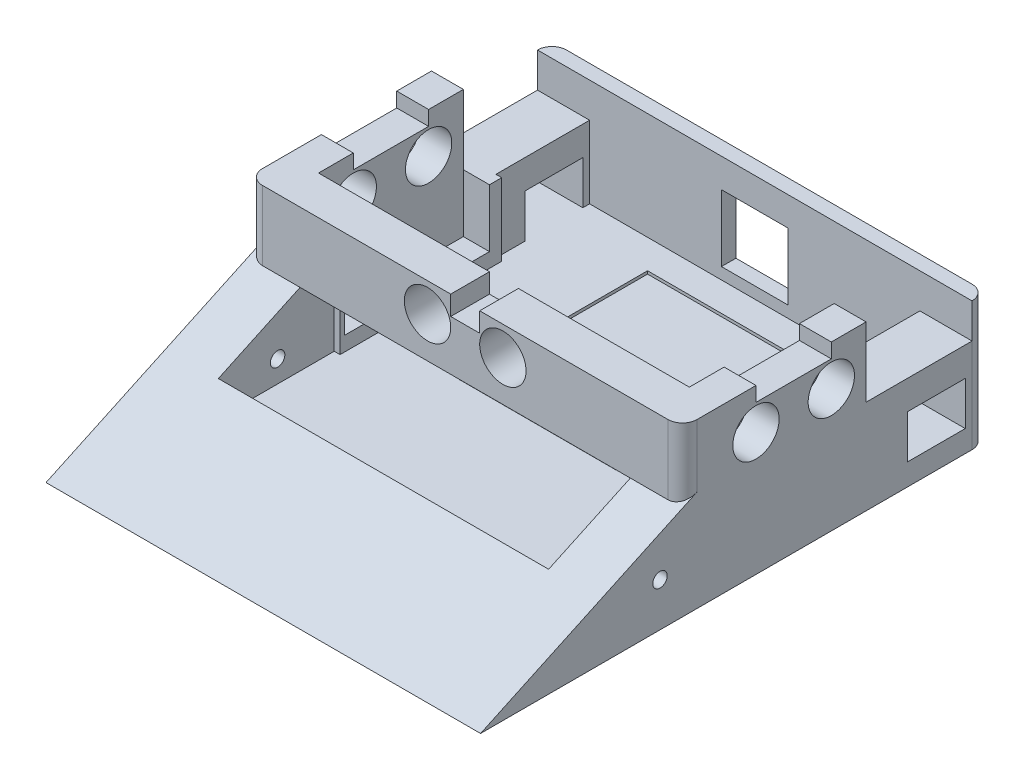
SolidWorks part; units mm, degrees
ref_plane "Front Plane" through (0, 0, 0) normal (0, 0, 1) x (1, 0, 0)
ref_plane "Top Plane" through (0, 0, 0) normal (0, 1, 0) x (1, 0, 0)
ref_plane "Right Plane" through (0, 0, 0) normal (1, 0, 0) x (0, 0, -1)
sketch "Sketch1" plane through (0, 0, 0) normal (0, 1, 0) x (1, 0, 0)
  line L4 (0, 0) -> (150, 0)
  line L5 (150, 0) -> (150, 180)
  line L6 (150, 180) -> (0, 180)
  line L7 (0, 180) -> (0, 0)
extrude "Boss-Extrude2" add sketch "Sketch1" along normal blind 7.5 contours L7 L4 L5 L6
sketch "Sketch2" plane through (150, 0, 0) normal (1, 0, 0) x (0, 0, -1)
  line L0 (180, 7.5) -> (50, 7.5)
  line L2 (50, 7.5) -> (56.85, 7.5)
  line L6 (56.85, 7.5) -> (56.85, 22.5)
  line L7 (56.85, 22.5) -> (76.85, 22.5)
  line L8 (76.85, 22.5) -> (76.85, 7.5)
  line L9 (76.85, 7.5) -> (86.85, 7.5)
  line L10 (86.85, 7.5) -> (86.85, 32.5)
  line L11 (86.85, 32.5) -> (46.85, 32.5)
  line L12 (46.85, 32.5) -> (46.85, 7.5)
  line L13 (46.85, 7.5) -> (56.85, 7.5)
  line L14 (180, 7.5) -> (172.6599, 7.5)
  line L15 (172.6599, 7.5) -> (172.6599, 22.5)
  line L16 (172.6599, 22.5) -> (152.6599, 22.5)
  line L17 (152.6599, 22.5) -> (152.6599, 7.5)
  line L18 (152.6599, 7.5) -> (142.6599, 7.5)
  line L19 (142.6599, 7.5) -> (142.6599, 32.5)
  line L20 (142.6599, 32.5) -> (180, 32.5)
  line L21 (180, 32.5) -> (180, 7.5)
  line M8 (180, 7.5) -> (0, 7.5)
extrude "Boss-Extrude4" add sketch "Sketch2" against normal blind 18 contours L11 L12 L0 L6 L7 L8 L10 M8 | L21 L20 L19 L17 L16 L15 M8 region at (150, 7.9717, -81.85) region at (150, 7.9494, -176.3299)
sketch "Sketch4" plane through (0, 0, 0) normal (-1, 0, 0) x (0, 0, 1)
  line L0 (-180, 7.5) -> (-180, 32.5)
  line L1 (-180, 32.5) -> (-142.6599, 32.5)
  line L2 (-142.6599, 32.5) -> (-142.6599, 7.5)
  line L3 (-142.6599, 7.5) -> (-152.6599, 7.5)
  line L4 (-152.6599, 7.5) -> (-152.6599, 22.5)
  line L5 (-152.6599, 22.5) -> (-172.6599, 22.5)
  line L6 (-172.6599, 22.5) -> (-172.6599, 7.5)
  line L7 (-172.6599, 7.5) -> (-180, 7.5)
  line L8 (-86.85, 7.5) -> (-86.85, 32.5)
  line L9 (-86.85, 32.5) -> (-46.85, 32.5)
  line L10 (-46.85, 32.5) -> (-46.85, 7.5)
  line L11 (-46.85, 7.5) -> (-56.85, 7.5)
  line L12 (-56.85, 7.5) -> (-56.85, 22.5)
  line L13 (-56.85, 22.5) -> (-76.85, 22.5)
  line L14 (-76.85, 22.5) -> (-76.85, 7.5)
  line L15 (-76.85, 7.5) -> (-86.85, 7.5)
extrude "Boss-Extrude5" add sketch "Sketch4" against normal blind 18
sketch "Sketch6" plane through (150, 0, 0) normal (1, 0, 0) x (0, 0, -1)
  line L1 (56.85, 7.5) -> (76.85, 7.5)
  line L2 (56.85, 7.5) -> (56.85, 22.5)
  line L3 (56.85, 22.5) -> (76.85, 22.5)
  line L4 (76.85, 7.5) -> (76.85, 22.5)
extrude "Boss-Extrude7" add sketch "Sketch6" against normal blind 18
sketch "Sketch7" plane through (150, 0, 0) normal (1, 0, 0) x (0, 0, -1)
  line L1 (162.6599, 22.5) -> (162.6599, 7.5) construction
  line L2 (172.6599, 22.5) -> (152.6599, 22.5) construction
  line L3 (152.6599, 15) -> (172.6599, 15) construction
  line L4 (152.6599, 22.5) -> (152.6599, 7.5) construction
  line L5 (172.6599, 7.5) -> (172.6599, 22.5) construction
  circle A0 centre (67.3, 15) radius 2.5
extrude "Boss-Extrude8" add sketch "Sketch7" along normal blind 22 and the other way blind 172
sketch "Sketch8" plane through (0, 0, 0) normal (-1, 0, 0) x (0, 0, 1)
  line L1 (-76.85, 7.5) -> (-56.85, 7.5)
  line L2 (-76.85, 7.5) -> (-76.85, 22.5)
  line L3 (-76.85, 22.5) -> (-56.85, 22.5)
  line L4 (-56.85, 7.5) -> (-56.85, 22.5)
extrude "Boss-Extrude9" add sketch "Sketch8" against normal blind 18
sketch "Sketch9" plane through (150, 0, 0) normal (1, 0, 0) x (0, 0, -1)
  line L0 (86.85, 32.5) -> (142.6599, 32.5)
  line L1 (142.6599, 32.5) -> (142.6599, 7.5)
  line L2 (142.6599, 7.5) -> (86.85, 7.5)
  line L3 (86.85, 7.5) -> (86.85, 32.5)
extrude "Boss-Extrude10" add sketch "Sketch9" against normal blind 20
sketch "Sketch10" plane through (0, 0, 0) normal (-1, 0, 0) x (0, 0, 1)
  line L1 (-142.6599, 7.5) -> (-86.85, 7.5)
  line L2 (-142.6599, 7.5) -> (-142.6599, 32.5)
  line L3 (-142.6599, 32.5) -> (-86.85, 32.5)
  line L4 (-86.85, 7.5) -> (-86.85, 32.5)
extrude "Boss-Extrude11" add sketch "Sketch10" against normal blind 20
chamfer "Chamfer2" distance 10 angle 65 1 edges at (75, 7.5, 0) first distance on face at (75, 3.75, 0)
sketch "Sketch12" plane through (150, 0, 0) normal (1, 0, 0) x (0, 0, -1)
  line L0 (113.425, 32.5) -> (126.425, 32.5)
  line L3 (180, 32.5) -> (46.85, 32.5) construction
  line L4 (113.425, 32.5) -> (100.425, 32.5)
  line L8 (88.425, 42.5) -> (88.425, 32.5)
  line L9 (88.425, 42.5) -> (88.425, 54.5)
  line L11 (138.425, 42.5) -> (138.425, 54.5)
  line L12 (138.425, 54.5) -> (88.425, 54.5)
  line L13 (138.425, 42.5) -> (138.425, 32.5)
  line L14 (138.425, 32.5) -> (88.425, 32.5)
  circle A1 centre (100.425, 42.5) radius 8
  circle A2 centre (126.425, 42.5) radius 8
  line M13 (180, 32.5) -> (46.85, 32.5)
extrude "Boss-Extrude12" add sketch "Sketch12" against normal blind 11 contours L13 L11 L12 L9 L8 A2 A1 M13 region at (150, 44.0762, -113.425)
sketch "Sketch13" plane through (150, 0, 0) normal (1, 0, 0) x (0, 0, -1)
  line L0 (88.425, 54.5) -> (88.425, 56.5)
  line L1 (88.425, 54.5) -> (138.425, 54.5)
  line L2 (138.425, 54.5) -> (138.425, 56.5)
  line L3 (138.425, 56.5) -> (88.425, 56.5)
extrude "Boss-Extrude13" add sketch "Sketch13" against normal blind 11
sketch "Sketch14" plane through (150, 0, 0) normal (1, 0, 0) x (0, 0, -1)
  line L0 (100.425, 51.4481) -> (100.425, 55.8735)
  line L1 (126.425, 51.4481) -> (126.425, 55.8735)
  line L2 (126.425, 55.8735) -> (100.425, 55.8735)
  line L3 (100.425, 51.4481) -> (126.425, 51.4481)
extrude "Cut-Extrude1" cut sketch "Sketch14" against normal blind 11
sketch "Sketch15" plane through (0, 32.5, 0) normal (0, 1, 0) x (1, 0, 0)
  line L0 (130, 142.6599) -> (130, 86.85) construction
  line L1 (139, 138.425) -> (130, 138.425)
  line L2 (139, 138.425) -> (139, 88.441)
  line L3 (139, 88.441) -> (130, 88.441)
  line L4 (130, 138.425) -> (130, 88.441)
extrude "Cut-Extrude2" cut sketch "Sketch15" against normal blind 20
sketch "Sketch16" plane through (0, 0, 0) normal (-1, 0, 0) x (0, 0, 1)
  line L0 (-126.425, 55.8735) -> (-126.425, 51.4481)
  line L1 (-126.425, 51.4481) -> (-100.425, 51.4481)
  line L2 (-100.425, 51.4481) -> (-100.425, 55.8735)
  line L3 (-100.425, 55.8735) -> (-126.425, 55.8735)
  line L5 (-138.425, 32.5) -> (-88.425, 32.5)
  line L6 (-138.425, 32.5) -> (-138.425, 56.5)
  line L7 (-138.425, 56.5) -> (-88.425, 56.5)
  line L8 (-88.425, 32.5) -> (-88.425, 56.5)
  circle A0 centre (-126.425, 42.5) radius 8
  circle A1 centre (-100.425, 42.5) radius 8
extrude "Boss-Extrude14" add sketch "Sketch16" against normal blind 11
sketch "Sketch17" plane through (0, 32.5, 0) normal (0, 1, 0) x (1, 0, 0)
  line L0 (20, 86.85) -> (20, 142.6599) construction
  line L1 (11, 138.425) -> (20, 138.425)
  line L2 (11, 138.425) -> (11, 88.4285)
  line L3 (11, 88.4285) -> (20, 88.4285)
  line L4 (20, 138.425) -> (20, 88.4285)
extrude "Cut-Extrude3" cut sketch "Sketch17" against normal blind 20
sketch "Sketch20" plane through (0, 7.5, 0) normal (0, 1, 0) x (1, 0, 0)
  line L0 (18, 180) -> (18, 175)
  line L1 (18, 142.6599) -> (18, 180) construction
  line L2 (18, 175) -> (132, 175)
  line L3 (132, 180) -> (132, 172.6599) construction
  line L4 (132, 175) -> (132, 180)
  line L5 (132, 180) -> (18, 180)
extrude "Boss-Extrude15" add sketch "Sketch20" along normal blind 25
sketch "Sketch21" plane through (0, 7.5, 0) normal (0, 1, 0) x (1, 0, 0)
  line L0 (75, 175) -> (75, 165)
  line L1 (18, 175) -> (132, 175) construction
  line L2 (75, 165) -> (102, 165)
  line L3 (102, 165) -> (102, 100)
  line L4 (102, 100) -> (48, 100)
  line L5 (48, 100) -> (48, 165)
  line L6 (48, 165) -> (75, 165)
extrude "Cut-Extrude4" cut sketch "Sketch21" against normal blind 1 contours L6 L5 L4 L3 L2 region at (75, 7.5, -132.5)
sketch "Sketch22" plane through (150, 0, 0) normal (1, 0, 0) x (0, 0, -1)
  line L0 (21.4451, 7.5) -> (46.85, 19.3465)
  line L1 (46.85, 32.5) -> (46.85, 7.5) construction
  line L2 (46.85, 19.3465) -> (75.0577, 32.5)
  line L3 (88.425, 32.5) -> (46.85, 32.5) construction
  line L4 (75.0577, 32.5) -> (21.4451, 32.5)
  line L5 (21.4451, 32.5) -> (21.4451, 7.5)
extrude "Cut-Extrude5" cut sketch "Sketch22" against normal blind 20
sketch "Sketch23" plane through (150, 0, 0) normal (1, 0, 0) x (0, 0, -1)
  line L0 (21.4451, 7.5) -> (46.85, 19.3465)
  line L1 (46.85, 19.3465) -> (46.85, 7.5)
  line L2 (46.85, 7.5) -> (21.4451, 7.5)
extrude "Boss-Extrude16" add sketch "Sketch23" against normal blind 50
sketch "Sketch24" plane through (0, 0, 0) normal (-1, 0, 0) x (0, 0, 1)
  line L0 (-21.4451, 7.5) -> (-75.0577, 32.5)
  line L1 (-21.4451, 7.5) -> (-21.4451, 32.5)
  line L2 (-21.4451, 32.5) -> (-75.0577, 32.5)
extrude "Cut-Extrude6" cut sketch "Sketch24" against normal blind 50
sketch "Sketch25" plane through (0, 0, 0) normal (-1, 0, 0) x (0, 0, 1)
  line L0 (-46.85, 19.3465) -> (-46.85, 7.5)
  line L1 (-46.85, 7.5) -> (-21.4451, 7.5)
  line L2 (-21.4451, 7.5) -> (-46.85, 19.3465)
extrude "Boss-Extrude17" add sketch "Sketch25" against normal blind 50
sketch "Sketch27" plane through (0, 0, -180) normal (0, 0, -1) x (-1, 0, 0)
  line L0 (-150, 32.5) -> (-150, 44.5)
  line L1 (-150, 56.5) -> (-150, 32.5) construction
  line L2 (-150, 44.5) -> (0, 44.5)
  line L3 (0, 56.5) -> (0, 32.5) construction
  line L4 (0, 44.5) -> (0, 32.5)
  line L5 (0, 32.5) -> (-150, 32.5)
extrude "Boss-Extrude18" add sketch "Sketch27" against normal blind 5
sketch "Sketch28" plane through (0, 0, -180) normal (0, 0, -1) x (-1, 0, 0)
  line L2 (-75, 34.5) -> (-63.5, 34.5)
  line L3 (-63.5, 34.5) -> (-63.5, 11.5)
  line L4 (-63.5, 11.5) -> (-86.5, 11.5)
  line L5 (-86.5, 11.5) -> (-86.5, 34.5)
  line L6 (-86.5, 34.5) -> (-75, 34.5)
extrude "Cut-Extrude7" cut sketch "Sketch28" against normal blind 5
sketch "Sketch29" plane through (0, 32.5, 0) normal (0, 1, 0) x (1, 0, 0)
  line L1 (0, 75.0577) -> (150, 75.0577)
  line L2 (0, 75.0577) -> (0, 88.425)
  line L3 (0, 88.425) -> (150, 88.425)
  line L4 (150, 75.0577) -> (150, 88.425)
extrude "Boss-Extrude19" add sketch "Sketch29" along normal blind 24
sketch "Sketch30" plane through (0, 7.5, 0) normal (0, 1, 0) x (1, 0, 0)
  line L1 (50, 21.4451) -> (100, 21.4451)
  line L2 (50, 21.4451) -> (50, 46.85)
  line L3 (50, 46.85) -> (100, 46.85)
  line L4 (100, 21.4451) -> (100, 46.85)
extrude "Boss-Extrude20" add sketch "Sketch30" along normal blind 12
sketch "Sketch31" plane through (100, 0, 0) normal (1, 0, 0) x (0, 0, -1)
  line L0 (48.3642, 20.0526) -> (21.3289, 20.0526)
  line L1 (75.0577, 32.5) -> (5.3613, 0) construction
  line L2 (21.3289, 20.0526) -> (21.4451, 7.5)
  line L3 (21.4451, 7.5) -> (48.3642, 20.0526)
extrude "Cut-Extrude10" cut sketch "Sketch31" against normal blind 50
sketch "Sketch32" plane through (0, 0, -75.0577) normal (0, 0, 1) x (1, 0, 0)
  circle A0 centre (62, 46.5) radius 8
  circle A1 centre (88, 46.5) radius 8
  point P1 (0, 0)
extrude "Cut-Extrude13" cut sketch "Sketch32" against normal blind 50
sketch "Sketch33" plane through (0, 0, -75.0577) normal (0, 0, 1) x (1, 0, 0)
  line L0 (0, 56.5) -> (150, 56.5) construction
  line L1 (70, 56.5) -> (80, 56.5)
  line L2 (70, 56.5) -> (70, 49.7983)
  line L3 (70, 49.7983) -> (80, 49.7983)
  line L4 (80, 56.5) -> (80, 49.7983)
extrude "Cut-Extrude14" cut sketch "Sketch33" against normal blind 50
fillet "Fillet1" radius 5 1 edges at (0, 44.5, -75.0577)
fillet "Fillet2" radius 5 1 edges at (150, 44.5, -75.0577)
fillet "Fillet3" radius 5 1 edges at (150, 22.25, -180)
fillet "Fillet4" radius 5 1 edges at (0, 22.25, -180)
sketch "Sketch34" plane through (-22, 0, 0) normal (-1, 0, 0) x (0, 0, 1)
  circle A0 centre (-67.3, 15) radius 2.5
extrude "Cut-Extrude15" cut sketch "Sketch34" against normal blind 200
sketch "Sketch35" plane through (0, 0, 0) normal (-1, 0, 0) x (0, 0, 1)
  line L0 (-126.425, 55.8735) -> (-126.425, 56.5)
  line L1 (-80.0577, 56.5) -> (-138.425, 56.5) construction
  line L2 (-126.425, 56.5) -> (-100.5054, 56.5)
  line L3 (-100.5054, 56.5) -> (-100.425, 55.8735)
  line L4 (-100.425, 55.8735) -> (-126.425, 55.8735)
extrude "Cut-Extrude16" cut sketch "Sketch35" against normal blind 200
sketch "Sketch36" plane through (0, 0, 0) normal (-1, 0, 0) x (0, 0, 1)
  line L0 (-100.425, 55.8735) -> (-100.425, 56.5)
  line L1 (-80.0577, 56.5) -> (-100.5054, 56.5) construction
  line L2 (-100.425, 56.5) -> (-100.5054, 56.5)
  line L3 (-100.5054, 56.5) -> (-100.425, 55.8735)
extrude "Cut-Extrude17" cut sketch "Sketch36" against normal blind 200
